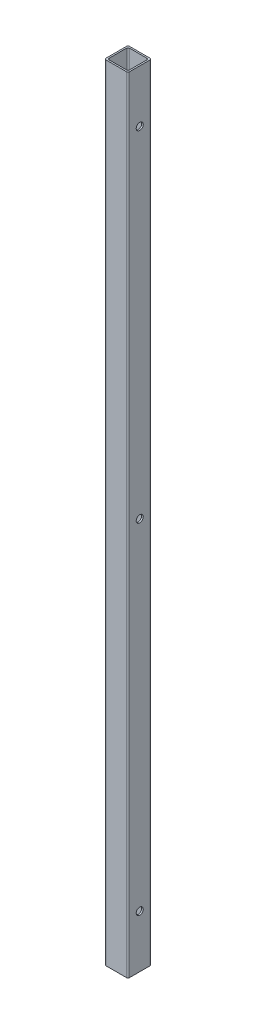
SolidWorks part; units mm, degrees
ref_plane "Front Plane" through (0, 0, 0) normal (0, 0, 1) x (1, 0, 0)
ref_plane "Top Plane" through (0, 0, 0) normal (0, 1, 0) x (1, 0, 0)
ref_plane "Right Plane" through (0, 0, 0) normal (1, 0, 0) x (0, 0, -1)
sketch "Sketch1" plane through (0, 0, 0) normal (0, 1, 0) x (1, 0, 0)
  line L0 (8.382, -8.382) -> (8.382, 8.382)
  line L1 (-9.652, -9.652) -> (9.652, -9.652)
  line L2 (-9.652, -9.652) -> (-9.652, 9.652)
  line L3 (-9.652, 9.652) -> (9.652, 9.652)
  line L4 (9.652, -9.652) -> (9.652, 9.652)
  line L5 (-9.652, -9.652) -> (9.652, 9.652) construction
  line L6 (-9.652, 9.652) -> (9.652, -9.652) construction
  line L7 (-8.382, 8.382) -> (8.382, 8.382)
  line L8 (-8.382, -8.382) -> (-8.382, 8.382)
  line L9 (-8.382, -8.382) -> (8.382, -8.382)
  point P0 (0, 0)
  dimension "D1" = 19.304
  dimension "D2" = 1.27
extrude "Boss-Extrude1" add sketch "Sketch1" along normal blind 645.16
fillet "Fillet1" radius 1.27 8 edges at (-9.652, 322.58, 9.652) (-9.652, 322.58, -9.652) (9.652, 322.58, -9.652) (9.652, 322.58, 9.652) (-8.382, 322.58, -8.382) (8.382, 322.58, 8.382) (8.382, 322.58, -8.382) (-8.382, 322.58, 8.382)
hole_wizard "#1 (0.228) Diameter Hole1" positions "Sketch2" profile "Sketch3" hole size "#1" standard "ANSI Inch" end condition through all
sketch "Sketch2" plane through (9.652, 0, 0) normal (1, 0, 0) x (0, 0, -1)
  line L0 (0, 645.16) -> (0, 0) construction
  line L1 (-8.382, 645.16) -> (8.382, 645.16) construction
  point P8 (0, 601.98)
  point P82 (0, 322.58)
  point P83 (0, 43.18)
  dimension "D1" = 43.18
  dimension "D2" = 3
sketch "Sketch3" plane through (9.652, 43.18, 0) normal (0, 1, 0) x (0, 0, -1)
  line L0 (0, 0) -> (0, 19.304)
  line L1 (0, 19.304) -> (2.8956, 19.304)
  line L2 (2.8956, 19.304) -> (2.8956, 0)
  line L5 (2.8956, 0) -> (0, 0)
  line L11 (0, -6.35) -> (0, 107.95) construction
  dimension "Thru Hole Dia." = 5.7912
  dimension "Thru Hole Depth" = 19.304
